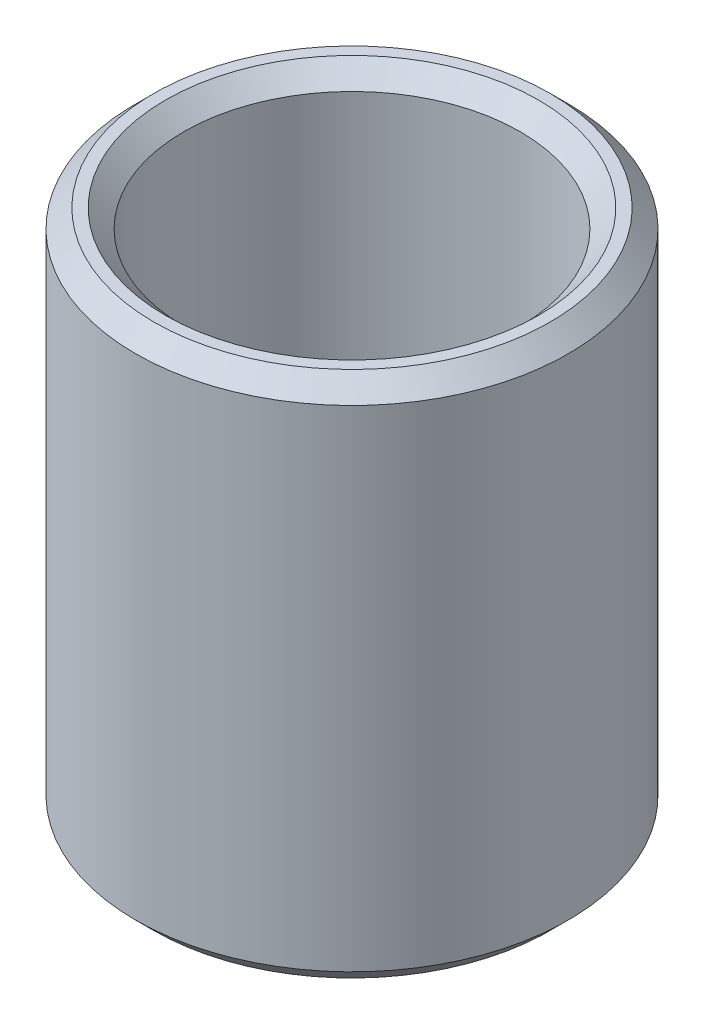
SolidWorks part; units mm, degrees
ref_plane "Front Plane" through (0, 0, 0) normal (0, 0, 1) x (1, 0, 0)
ref_plane "Top Plane" through (0, 0, 0) normal (0, 1, 0) x (1, 0, 0)
ref_plane "Right Plane" through (0, 0, 0) normal (1, 0, 0) x (0, 0, -1)
sketch "Sketch1" plane through (0, 0, 0) normal (0, 1, 0) x (1, 0, 0)
  circle A0 centre (0, 0) radius 42.5
  dimension "SLEEVE_OD" = 85
extrude "Boss-Extrude1" add sketch "Sketch1" along normal blind 103.5109
sketch "Sketch2" plane through (0, 0, 0) normal (0, 1, 0) x (1, 0, 0)
  circle A0 centre (0, 0) radius 33.0458
  dimension "BORE_D" = 66.0917
extrude "Cut-Extrude1" cut sketch "Sketch2" along normal through all
chamfer "Chamfer1" distance 3.5914 angle 45 4 edges at (0, 103.5109, 33.0458) (0, 0, 33.0458) (0, 0, 42.5) (0, 103.5109, 42.5)
